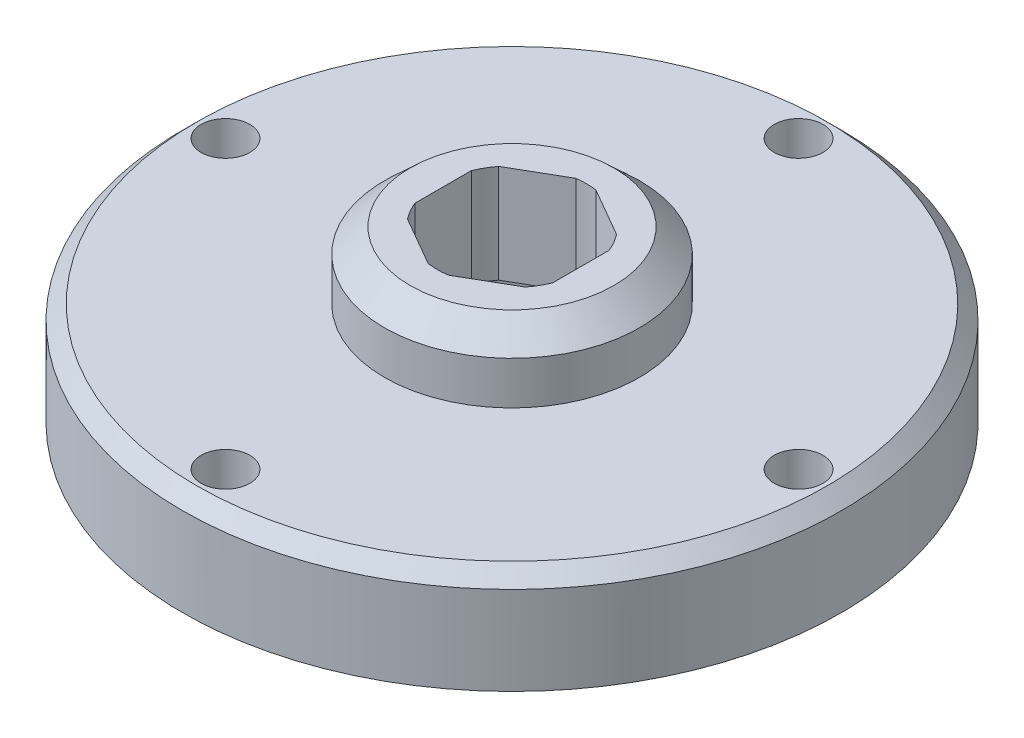
SolidWorks part; units mm, degrees
ref_plane "Front Plane" through (0, 0, 0) normal (0, 0, 1) x (1, 0, 0)
ref_plane "Top Plane" through (0, 0, 0) normal (0, 1, 0) x (1, 0, 0)
ref_plane "Right Plane" through (0, 0, 0) normal (1, 0, 0) x (0, 0, -1)
sketch "Sketch1" plane through (0, 0, 0) normal (0, 0, 1) x (1, 0, 0)
  line L0 (6.8, 0) -> (6.8, 4.953)
  line L1 (6.8, 4.953) -> (5.2, 4.953)
  line L2 (5.2, 4.953) -> (5.2, 11.829)
  line L3 (5.2, 11.829) -> (7.112, 11.829)
  line L5 (8.9, 7.1665) -> (23, 7.1665)
  line L6 (23, 7.1665) -> (23, 0)
  line L7 (23, 0) -> (6.8, 0)
  line L8 (7.112, 11.829) -> (8.9, 10.1665)
  line L9 (8.9, 10.1665) -> (8.9, 7.1665)
  line L10 (0, 0) -> (0, 16.4092) construction
  dimension "D1" = 6.8
  dimension "D2" = 23
  dimension "D3" = 4.953
  dimension "D4" = 8.9
  dimension "D5" = 11.829
  dimension "D6" = 7.1665
  dimension "D7" = 3
  dimension "D8" = 7.112
  dimension "D9" = 5.2
revolve "Revolve1" add sketch "Sketch1" angle 360 about L10
sketch "Sketch2" plane through (0, 0, 0) normal (0, 1, 0) x (1, 0, 0)
  circle A0 centre (0, 0) radius 20 construction
  point P3 (-20, 0)
  dimension "D1" = 40
hole_wizard "M3 Clearance Hole1" positions "Sketch2" profile "Sketch3" hole size "M3" standard "ANSI Metric" end condition through all
sketch "Sketch3" plane through (-20, 0, 0) normal (1, 0, 0) x (0, 0, -1)
  line L0 (0, 0) -> (0, 11.829)
  line L1 (0, 11.829) -> (1.7, 11.829)
  line L2 (1.7, 11.829) -> (1.7, 0)
  line L5 (1.7, 0) -> (0, 0)
  line L11 (0, -6.35) -> (0, 107.95) construction
  dimension "Thru Hole Dia." = 3.4
  dimension "Thru Hole Depth" = 11.829
pattern_circular "CirPattern1" count 4 over 360 about axis through (0, 0, 0) along (0, -1, 0) of "M3 Clearance Hole1"
sketch "Sketch4" plane through (0, 4.953, 0) normal (0, -1, 0) x (1, 0, 0)
  line L1 (4.8125, 2.7785) -> (0, 5.557)
  line L2 (0, 5.557) -> (-4.8125, 2.7785)
  line L3 (-4.8125, 2.7785) -> (-4.8125, -2.7785)
  line L4 (-4.8125, -2.7785) -> (0, -5.557)
  line L5 (0, -5.557) -> (4.8125, -2.7785)
  line L6 (4.8125, -2.7785) -> (4.8125, 2.7785)
  circle A0 centre (0, 0) radius 4.8125 construction
  circle A1 centre (0, 0) radius 5.2 construction
  circle A2 centre (0, 0) radius 5.2
  circle M9 centre (0, 0) radius 5.2
  dimension "D1" = 9.625
extrude "Boss-Extrude1" add sketch "Sketch4" against normal up to surface (6.876 mm away) contours L2 M9 | L3 M9 | L4 M9 | L5 M9 | L6 M9 | L1 M9 region at (2.484, 4.953, 4.3024) region at (4.968, 4.953, 0) region at (-2.484, 4.953, 4.3024) region at (2.484, 4.953, -4.3024) region at (-4.968, 4.953, 0) region at (-2.484, 4.953, -4.3024) up to face at (0, 11.829, -5.2)
chamfer "Chamfer1" distance 0.75 angle 45 1 edges at (0, 0, -6.8)
chamfer "Chamfer2" distance 1 angle 45 1 edges at (0, 7.1665, -23)
